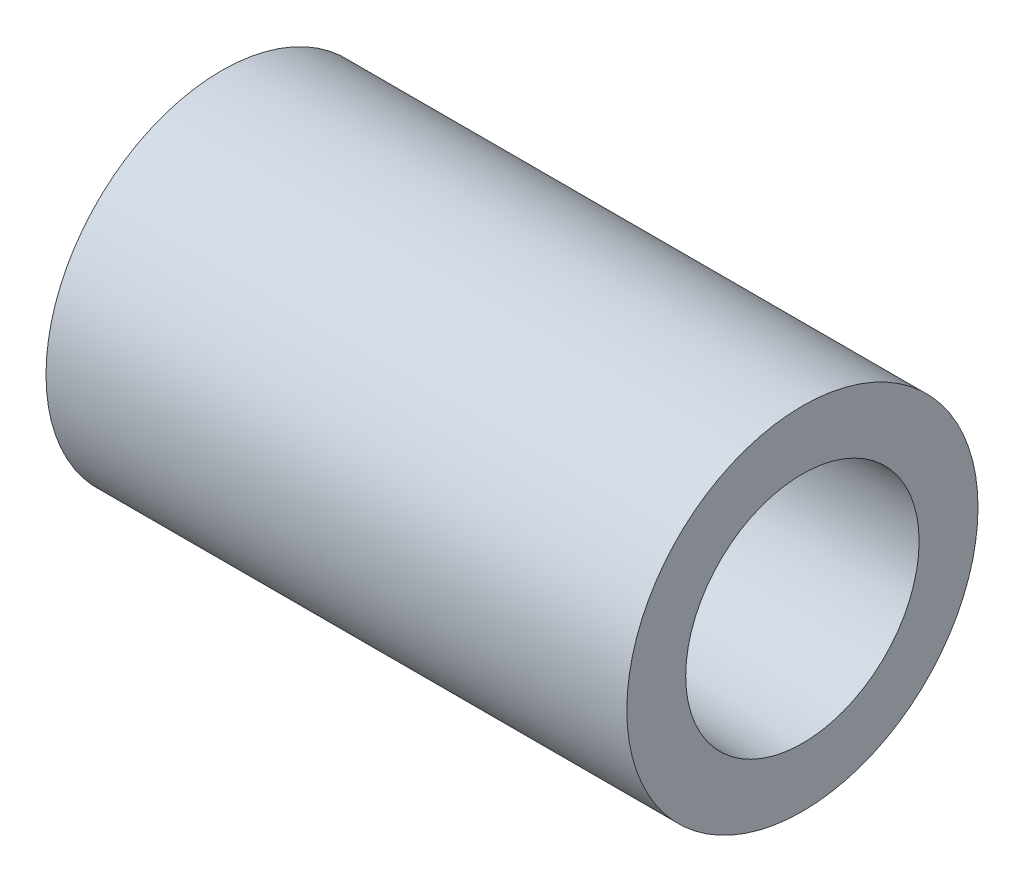
SolidWorks part; units mm, degrees
material "PVC Rigid"
ref_plane "Front Plane" through (0, 0, 0) normal (0, 0, 1) x (1, 0, 0)
ref_plane "Top Plane" through (0, 0, 0) normal (0, 1, 0) x (1, 0, 0)
ref_plane "Right Plane" through (0, 0, 0) normal (1, 0, 0) x (0, 0, -1)
sketch "Sketch0" plane through (0, 0, 0) normal (0, 0, 1) x (1, 0, 0)
  line L0 (-17.0656, 0) -> (0, 0) construction
  line L2 (-1.9844, 0) -> (0, 0) construction
  line L3 (0, 0) -> (0, 10.3188) construction
  line L4 (-17.0656, 10.3187) -> (-17.0656, -10.3187) construction
  line L5 (-1.9844, 6.3884) -> (-17.0656, 6.858) construction
  line L6 (-1.9844, 6.3884) -> (-1.9844, -6.3884) construction
  line L7 (-1.9844, -6.3884) -> (-17.0656, -6.858) construction
  line L8 (-17.0656, 6.858) -> (-17.0656, -6.858) construction
  line L10 (0, 10.3188) -> (0, -10.3188) construction
  line L13 (-6.8599, 6.5402) -> (-6.8599, -6.5402) construction
  line L14 (-1.9844, -3.3658) -> (-1.9844, 3.3658) construction
  point P29 (-6.8599, 0)
sketch "Sketch1" plane through (0, 0, 0) normal (0, 0, 1) x (1, 0, 0)
  line L0 (-17.0656, 0) -> (0, 0) construction
  line L1 (-17.0656, 0) -> (0, 0) construction
  line L3 (-17.0656, -10.3187) -> (-1.9844, -10.3188)
  line L4 (-17.0656, -10.3187) -> (-17.0656, -6.858)
  line L5 (-17.0656, -6.858) -> (-1.9844, -6.3884)
  line L6 (-1.9844, -10.3188) -> (-1.9844, -6.3884)
revolve "Revolve1" add sketch "Sketch1" angle 360 about L1
mirror "Mirror2" about plane through (0, 0, 0) normal (1, 0, 0) of bodies 102
sketch "Sketch3" plane through (-1.9844, 0, 0) normal (1, 0, 0) x (0, 0, -1)
  circle A0 centre (0, 0) radius 3.3658 construction
  circle A1 centre (0, 0) radius 10.3188
extrude "Boss-Extrude1" add sketch "Sketch3" along normal up to surface (3.9688 mm away) up to face at (1.9844, 0, 6.3884)
sketch "Sketch8" plane through (0, 0, 0) normal (0, 0, 1) x (1, 0, 0)
  line L0 (-17.0656, 0) -> (17.0656, 0)
  line L1 (17.0656, -10.3187) -> (17.0656, 10.3187) construction
  line L2 (-17.0656, 0) -> (-17.0656, -6.858)
  line L3 (-17.0656, -6.858) -> (-1.9844, -6.3884)
  line L4 (-1.9844, -6.3884) -> (-1.9844, -3.3658)
  line L5 (-1.9844, -3.3658) -> (1.9844, -3.3658)
  line L6 (0, 0) -> (0, -3.3658) construction
  line L7 (1.9844, -6.3884) -> (1.9844, -3.3658)
  line L8 (17.0656, -6.858) -> (1.9844, -6.3884)
  line L9 (17.0656, 0) -> (17.0656, -6.858)
revolve "Cut-Revolve1" cut sketch "Sketch8" angle 360 about L0
ref_axis "Axis1" [suppressed] through (0, 0, 11.3506) along (0, 0, -1)
sketch "Sketch9" plane through (0, 0, 0) normal (1, 0, 0) x (0, 0, -1)
  line L0 (0, 6.858) -> (0, -6.858) construction
  line L1 (0, 11.9151) -> (-10.3188, 5.9575)
  line L2 (-10.3188, 5.9575) -> (-10.3188, -5.9575)
  line L3 (-10.3188, -5.9575) -> (0, -11.9151)
  line L4 (0, -11.9151) -> (10.3187, -5.9575)
  line L5 (10.3187, -5.9575) -> (10.3187, 5.9575)
  line L6 (10.3187, 5.9575) -> (0, 11.9151)
  line L7 (0, 11.9151) -> (0, 0) construction
  line L9 (0, 10.3188) -> (-8.9363, 5.1594) construction
  line L10 (-8.9363, 5.1594) -> (-8.9363, -5.1594) construction
  line L11 (-8.9363, -5.1594) -> (0, -10.3187) construction
  line L12 (0, -10.3187) -> (8.9363, -5.1594) construction
  line L13 (8.9363, -5.1594) -> (8.9363, 5.1594) construction
  line L14 (8.9363, 5.1594) -> (0, 10.3188) construction
  circle A0 centre (0, 0) radius 10.3188 construction
  circle A1 centre (0, 0) radius 8.9363
extrude "Boss-Extrude2" [suppressed] add sketch "Sketch9" along normal mid plane 5.6885
equation "\"D1@Boss-Extrude2\" = \"L@Sketch0\" * 1 / 6"
